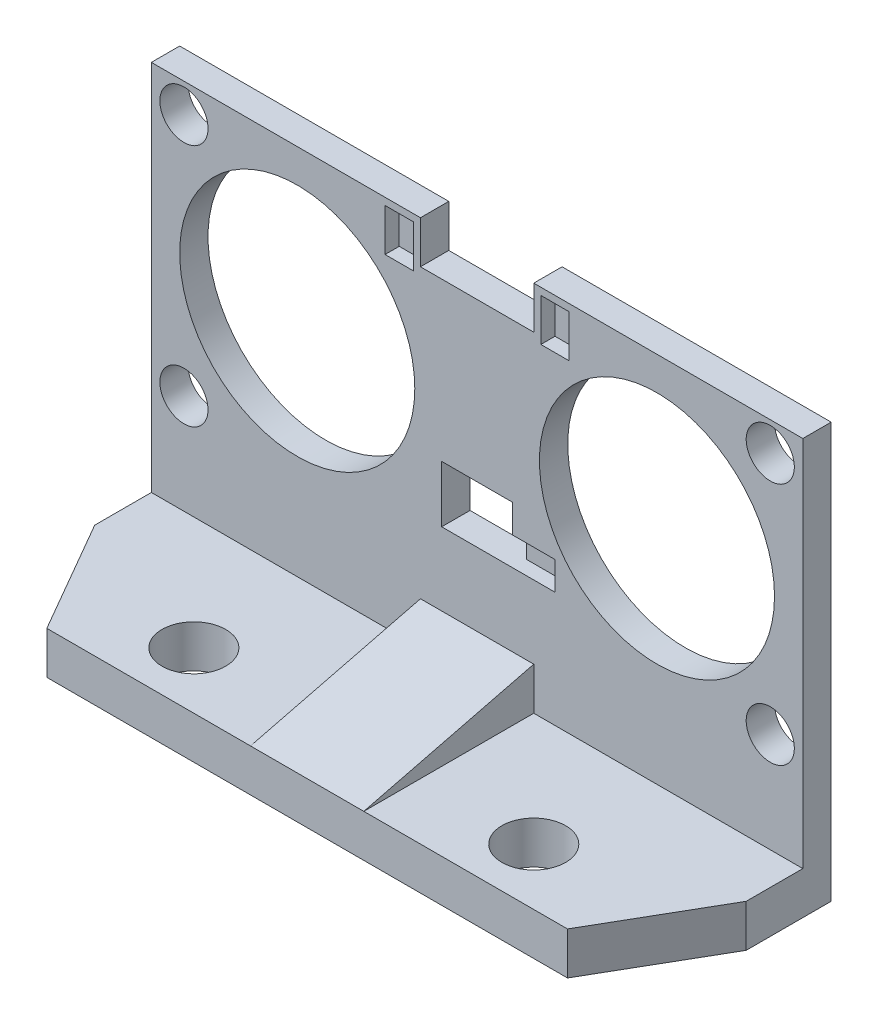
SolidWorks part; units mm, degrees
material "ABS"
ref_plane "前基準面" through (0, 0, 0) normal (0, 0, 1) x (1, 0, 0)
ref_plane "上基準面" through (0, 0, 0) normal (0, 1, 0) x (1, 0, 0)
ref_plane "右基準面" through (0, 0, 0) normal (1, 0, 0) x (0, 0, -1)
sketch "草圖1" plane through (0, 0, 0) normal (0, 0, 1) x (1, 0, 0)
  line L1 (-23, -10.65) -> (23, -10.65)
  line L2 (-23, -10.65) -> (-23, 10.65)
  line L3 (-23, 10.65) -> (23, 10.65)
  line L4 (23, -10.65) -> (23, 10.65)
  line L5 (-23, -10.65) -> (23, 10.65) construction
  line L6 (-23, 10.65) -> (23, -10.65) construction
  point P0 (0, 0)
  dimension "D1" = 46
  dimension "D2" = 21.3
extrude "填料-伸長1" add sketch "草圖1" along normal blind 2
sketch "草圖2" plane through (0, 0, 2) normal (0, 0, 1) x (1, 0, 0)
  line L0 (-12.7, 0) -> (12.7, 0) construction
  circle A0 centre (-12.7, 0) radius 8.3
  circle A1 centre (12.7, 0) radius 8.3
  point P4 (0, 0)
  dimension "D1" = 25.4
  dimension "D2" = 16.6
extrude "除料-伸長1" cut sketch "草圖2" against normal through all
sketch "草圖3" plane through (0, 0, 2) normal (0, 0, 1) x (1, 0, 0)
  line L0 (0, 0) -> (0, 9.15) construction
  line L1 (23, 10.65) -> (-23, 10.65) construction
  line L2 (-4, 7.65) -> (4, 7.65)
  line L3 (-4, 7.65) -> (-4, 10.65)
  line L4 (-4, 10.65) -> (4, 10.65)
  line L5 (4, 7.65) -> (4, 10.65)
  line L6 (-4, 7.65) -> (4, 10.65) construction
  line L7 (-4, 10.65) -> (4, 7.65) construction
  dimension "D1" = 8
  dimension "D2" = 3
extrude "除料-伸長2" cut sketch "草圖3" against normal through all
sketch "草圖4" plane through (0, 0, 2) normal (0, 0, 1) x (1, 0, 0)
  line L0 (0, 0) -> (0, -5.5) construction
  line L2 (-2.5, -3.5) -> (2.5, -3.5)
  line L3 (-2.5, -3.5) -> (-2.5, -7.5)
  line L4 (-2.5, -7.5) -> (2.5, -7.5)
  line L5 (2.5, -3.5) -> (2.5, -7.5)
  line L6 (-2.5, -3.5) -> (2.5, -7.5) construction
  line L7 (-2.5, -7.5) -> (2.5, -3.5) construction
  dimension "D1" = 5
  dimension "D2" = 4
  dimension "D3" = 5.5
extrude "除料-伸長3" cut sketch "草圖4" against normal through all
sketch "草圖5" plane through (0, 0, 2) normal (0, 0, 1) x (1, 0, 0)
  line L0 (0, 0) -> (0, 8.65) construction
  line L1 (2.5, -7.5) -> (5.5, -7.5)
  line L2 (2.5, -7.5) -> (2.5, -5.5)
  line L3 (2.5, -5.5) -> (5.5, -5.5)
  line L4 (5.5, -7.5) -> (5.5, -5.5)
  line L5 (-5.5, 8.65) -> (5.5, 8.65) construction
  line L6 (23, 10.65) -> (4, 10.65) construction
  line L7 (-4.5, 10.15) -> (-6.5, 10.15)
  line L8 (-4.5, 10.15) -> (-4.5, 7.15)
  line L9 (-4.5, 7.15) -> (-6.5, 7.15)
  line L10 (-6.5, 10.15) -> (-6.5, 7.15)
  line L11 (-4.5, 10.15) -> (-6.5, 7.15) construction
  line L12 (-4.5, 7.15) -> (-6.5, 10.15) construction
  line L13 (6.5, 10.15) -> (4.5, 10.15)
  line L14 (6.5, 10.15) -> (6.5, 7.15)
  line L15 (6.5, 7.15) -> (4.5, 7.15)
  line L16 (4.5, 10.15) -> (4.5, 7.15)
  line L17 (6.5, 10.15) -> (4.5, 7.15) construction
  line L18 (6.5, 7.15) -> (4.5, 10.15) construction
  point P10 (0, 8.65)
  dimension "D1" = 2
  dimension "D2" = 3
  dimension "D3" = 2
  dimension "D4" = 3
  dimension "D5" = 11
  dimension "D6" = 0.5
extrude "除料-伸長4" cut sketch "草圖5" against normal blind 1
sketch "草圖8" plane through (0, -10.65, 0) normal (0, -1, 0) x (1, 0, 0)
  line L1 (-23, 2) -> (23, 2)
  line L2 (-23, 2) -> (-23, 0)
  line L3 (-23, 0) -> (23, 0)
  line L4 (23, 2) -> (23, 0)
extrude "填料-伸長2" add sketch "草圖8" along normal blind 5
sketch "草圖9" plane through (0, -15.65, 0) normal (0, -1, 0) x (1, 0, 0)
  line L1 (-23, 0) -> (23, 0)
  line L2 (-23, 0) -> (-23, 14)
  line L3 (-23, 14) -> (23, 14)
  line L4 (23, 0) -> (23, 14)
  dimension "D1" = 14
extrude "填料-伸長3" add sketch "草圖9" along normal blind 3
hole_wizard "M3 餘隙孔1" positions "草圖6" profile "草圖7" hole size "M3" standard "Ansi Metric" end condition through all
sketch "草圖6" plane through (0, 0, 2) normal (0, 0, 1) x (1, 0, 0)
  line L1 (-20.7, -8.6) -> (20.7, -8.6) construction
  line L2 (-20.7, -8.6) -> (-20.7, 8.6) construction
  line L3 (-20.7, 8.6) -> (20.7, 8.6) construction
  line L4 (20.7, -8.6) -> (20.7, 8.6) construction
  line L5 (-20.7, -8.6) -> (20.7, 8.6) construction
  line L6 (-20.7, 8.6) -> (20.7, -8.6) construction
  point P1 (20.7, 8.6)
  point P112 (-20.7, -8.6)
  point P113 (-20.7, 8.6)
  point P114 (20.7, -8.6)
  dimension "D1" = 17.2
  dimension "D2" = 41.4
sketch "草圖7" plane through (20.7, 8.6, 2) normal (1, 0, 0) x (0, -1, 0)
  line L0 (0, 0) -> (0, 2)
  line L1 (0, 2) -> (1.7, 2)
  line L2 (1.7, 2) -> (1.7, 0)
  line L5 (1.7, 0) -> (0, 0)
  line L11 (0, -6.35) -> (0, 107.95) construction
  dimension "貫穿孔直徑" = 3.4
  dimension "貫穿孔深度" = 2
hole_wizard "M4 餘隙孔1" positions "草圖10" profile "草圖11" hole size "M4" standard "Ansi Metric" end condition through all
sketch "草圖10" plane through (0, -15.65, 0) normal (0, 1, 0) x (1, 0, 0)
  line L0 (0, -14) -> (0, -10) construction
  line L1 (23, -14) -> (-23, -14) construction
  line L4 (-12, -10) -> (12, -10) construction
  point P8 (-12, -10)
  point P9 (12, -10)
  dimension "D1" = 24
  dimension "D2" = 4
sketch "草圖11" plane through (12, -15.65, 10) normal (1, 0, 0) x (0, 0, 1)
  line L0 (0, 0) -> (0, 3)
  line L1 (0, 3) -> (2.25, 3)
  line L2 (2.25, 3) -> (2.25, 0)
  line L5 (2.25, 0) -> (0, 0)
  line L11 (0, -6.35) -> (0, 107.95) construction
  dimension "貫穿孔直徑" = 4.5
  dimension "貫穿孔深度" = 3
sketch "草圖13" plane through (0, 0, 0) normal (1, 0, 0) x (0, 0, -1)
  line L0 (-2, -12.65) -> (-14, -15.65)
  line L1 (-2, -15.65) -> (-2, 10.65) construction
  line L2 (-2, -15.65) -> (-14, -15.65) construction
  dimension "D1" = 3
rib "肋材1" sketch "草圖13" sketch "草圖13" thickness 8 extrusion direction parallel to sketch draft on no parameters "D1"=8
chamfer "導角1" distance 8 angle 30 2 edges at (-23, -17.15, 14) (23, -17.15, 14) first distance on face at (-23, -7.8833, 5.3333) first distance on face at (23, -7.8833, 5.3333)
